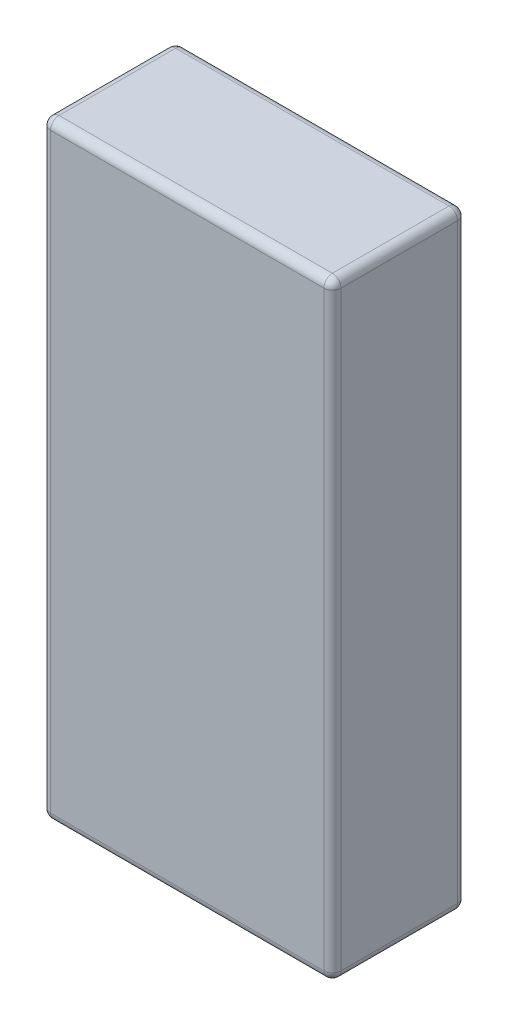
SolidWorks part; units mm, degrees
ref_plane "Front Plane" through (0, 0, 0) normal (0, 0, 1) x (1, 0, 0)
ref_plane "Top Plane" through (0, 0, 0) normal (0, 1, 0) x (1, 0, 0)
ref_plane "Right Plane" through (0, 0, 0) normal (1, 0, 0) x (0, 0, -1)
sketch "Sketch1" plane through (0, 0, 0) normal (0, 0, 1) x (1, 0, 0)
  line L1 (-16.95, -35.5) -> (16.95, -35.5)
  line L2 (-16.95, -35.5) -> (-16.95, 35.5)
  line L3 (-16.95, 35.5) -> (16.95, 35.5)
  line L4 (16.95, -35.5) -> (16.95, 35.5)
  line L5 (-16.95, -35.5) -> (16.95, 35.5) construction
  line L6 (-16.95, 35.5) -> (16.95, -35.5) construction
  point P0 (0, 0)
  dimension "D1" = 33.9
  dimension "D2" = 71
extrude "Boss-Extrude1" add sketch "Sketch1" along normal mid plane 15.6
fillet "Fillet1" radius 1 4 edges at (0, -35.5, -7.8) (0, -35.5, 7.8) (0, 35.5, -7.8) (0, 35.5, 7.8)
fillet "Fillet2" radius 1 16 edges at (-16.95, 35.2071, 7.5071) (-16.95, 35.5, 0) (-16.95, 35.2071, -7.5071) (-16.95, 0, -7.8) (-16.95, -35.2071, -7.5071) (-16.95, -35.5, 0) (-16.95, -35.2071, 7.5071) (16.95, -35.2071, 7.5071) (16.95, 0, 7.8) (16.95, 35.2071, 7.5071) (16.95, 35.5, 0) (16.95, 35.2071, -7.5071) (16.95, 0, -7.8) (16.95, -35.2071, -7.5071) (16.95, -35.5, 0) (-16.95, 0, 7.8)
ref_plane "Plane1" through (0, -11.5, 0) normal (0, -1, 0) x (-1, 0, 0)
sketch "Sketch2" [suppressed] plane through (0, -11.5, -642.6666) normal (0, -1, 0) x (1, 0, 0)
  line L0 (20.665, 669.3604) -> (16.165, 669.3604)
  line L1 (16.165, 669.3604) -> (16.165, 676.3604)
  line L2 (16.165, 676.3604) -> (15.365, 677.3604)
  line L3 (15.365, 677.3604) -> (21.465, 677.3604)
  line L4 (21.465, 677.3604) -> (20.665, 676.3604)
  line L5 (20.665, 676.3604) -> (20.665, 669.3604)
  line L6 (27.305, 669.3604) -> (14.605, 669.3604) construction
  line L7 (16.165, 676.3604) -> (16.165, 669.3604) construction
  dimension "D1" = 0.8
  dimension "D2" = 1
  dimension "D3" = 4.5
  dimension "D4" = 8
extrude "Boss-Extrude2" [suppressed] add sketch "Sketch2" along normal blind 8 from offset 0.2 separate body
sketch "Sketch3" [suppressed] plane through (0, 0, 34.6938) normal (0, 0, 1) x (1, 0, 0)
  line L1 (21.465, -19.7) -> (21.465, -11.7) construction
  line L2 (19.665, -14.55) -> (19.665, -14.85) construction
  line L3 (17.165, -16.55) -> (19.665, -16.55)
  line L4 (17.165, -16.55) -> (17.165, -14.85)
  line L5 (17.165, -14.85) -> (19.665, -14.85)
  line L6 (19.665, -16.55) -> (19.665, -14.85)
  line L7 (17.165, -16.55) -> (19.665, -14.85) construction
  line L8 (17.165, -14.85) -> (19.665, -16.55) construction
  line L9 (17.165, -12.85) -> (19.665, -12.85)
  line L10 (17.165, -12.85) -> (17.165, -14.55)
  line L11 (17.165, -14.55) -> (19.665, -14.55)
  line L12 (19.665, -12.85) -> (19.665, -14.55)
  line L13 (17.165, -12.85) -> (19.665, -14.55) construction
  line L14 (17.165, -14.55) -> (19.665, -12.85) construction
  line L15 (17.165, -18.55) -> (19.665, -18.55)
  line L16 (17.165, -18.55) -> (17.165, -16.85)
  line L17 (17.165, -16.85) -> (19.665, -16.85)
  line L18 (19.665, -18.55) -> (19.665, -16.85)
  line L19 (17.165, -18.55) -> (19.665, -16.85) construction
  line L20 (17.165, -16.85) -> (19.665, -18.55) construction
  line L21 (19.665, -16.55) -> (19.665, -16.85) construction
  line L23 (21.465, -11.7) -> (15.365, -11.7) construction
  point P0 (18.415, -11.7)
  point P1 (21.465, -15.7)
  point P4 (18.415, -15.7)
  point P7 (18.415, -15.7)
  point P12 (18.415, -13.7)
  point P17 (18.415, -17.7)
  dimension "D1" = 1.7
  dimension "D2" = 0.3
  dimension "D3" = 2.5
extrude "Cut-Extrude1" [suppressed] cut sketch "Sketch3" against normal blind 6
sketch "Sketch4" [suppressed] plane through (-11.7438, 0, 28.6938) normal (0, 0, -1) x (-1, 0, 0)
  line L0 (-30.1588, -17.7) -> (-30.1588, -15.7) construction
  line L1 (-30.1588, -15.7) -> (-30.1588, -13.7) construction
  line L3 (-28.9088, -14.85) -> (-28.9088, -16.55) construction
  circle A0 centre (-30.1588, -17.7) radius 0.65
  circle A1 centre (-30.1588, -15.7) radius 0.65
  circle A2 centre (-30.1588, -13.7) radius 0.65
  point P7 (-28.9088, -15.7)
  dimension "D1" = 1.3
  dimension "D2" = 2
sketch3d "3DSketch1" [suppressed]
  line L0 (18.415, -15.7, 34.6938) -> (18.415, -15.7, 28.6938)
  line L2 (10.3472, -32.5, 3.8) -> (14.95, -32.5, 3.8)
  spline S0 degree 3 poles (18.415, -15.7, 34.6938) (18.415, -15.7, 42.4421) (30.7848, -15.4677, 32.8828) (29.4715, -10.2255, 3.4658) (30.6716, -32.8263, 3.8042) (14.95, -32.5, 3.8) knots 0 0 0 0 0.553572 0.653572 1 1 1 1
  dimension "D1" = 2
  dimension "D2" = 3
  dimension "D3" = 4
  dimension "D4" = 13
sweep "Sweep1" [suppressed] add profiles "Sketch4" path "3DSketch1"
ref_plane "Plane3" [suppressed] through (0, 0, 16.78) normal (0, 0, -1) x (-1, 0, 0)
sketch "Sketch7" [suppressed] plane through (0, 0, 16.78) normal (0, 0, -1) x (-1, 0, 0)
  line L0 (-16.95, -34.5) -> (-16.95, 34.5) construction
  line L1 (15.95, -35.5) -> (-15.95, -35.5) construction
  line L2 (-16.95, -1.36) -> (-16.95, 34.5)
  line L3 (15.95, -35.5) -> (-15.95, -35.5)
  line L7 (-17.75, -1.36) -> (-25.75, -1.36)
  line L8 (-25.75, -1.36) -> (-25.75, 2.64)
  line L9 (-25.75, 2.64) -> (-17.75, 2.64)
  line L10 (-17.75, 2.64) -> (-17.75, -1.36)
  line L12 (-17.75, 2.64) -> (-25.75, 2.64)
  line L13 (-17.75, 2.64) -> (-17.75, -1.36)
  line L14 (-17.75, -1.36) -> (-25.75, -1.36)
  line L15 (-25.75, 2.64) -> (-25.75, -1.36)
  dimension "D2" = 8.8
  dimension "D3" = 4
  dimension "D4" = 8
ref_plane "Plane4" [suppressed] through (0, -1.36, 0) normal (0, -1, 0) x (-1, 0, 0)
sketch "Sketch8" [suppressed] plane through (0, -1.36, 0) normal (0, -1, 0) x (-1, 0, 0)
  line L0 (-16.95, -6.8) -> (-16.95, 6.8) construction
  line L1 (-16.95, -6.8) -> (-16.95, 6.8)
  line L2 (15.95, -7.8) -> (-15.95, -7.8) construction
  line L3 (15.95, -7.8) -> (-15.95, -7.8)
  line L4 (15.95, -7.8) -> (-15.95, -7.8)
  line L5 (-16.95, 6.8) -> (-16.95, -17.78)
  line L6 (-16.95, -17.78) -> (-25.75, -17.78)
  line L7 (-25.75, -17.78) -> (-17.75, -17.78)
  line L8 (-17.75, -17.78) -> (-17.75, -24.78)
  line L9 (-17.75, -24.78) -> (-25.75, -24.78)
  line L10 (-25.75, -24.78) -> (-25.75, -17.78)
  dimension "D1" = 8.8
  dimension "D2" = 8
